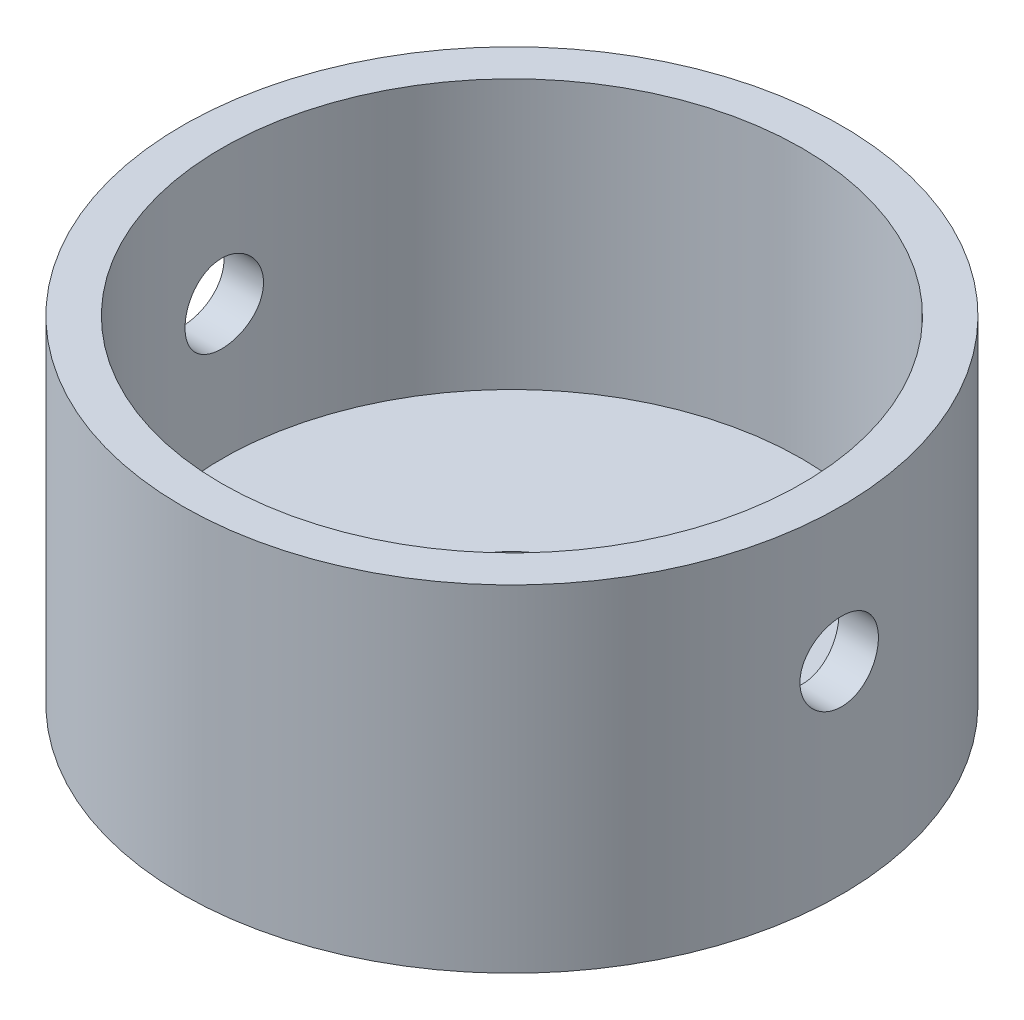
SolidWorks part; units mm, degrees
ref_plane "Front Plane" through (0, 0, 0) normal (0, 0, 1) x (1, 0, 0)
ref_plane "Top Plane" through (0, 0, 0) normal (0, 1, 0) x (1, 0, 0)
ref_plane "Right Plane" through (0, 0, 0) normal (1, 0, 0) x (0, 0, -1)
sketch "Sketch1" plane through (0, 0, 0) normal (0, 1, 0) x (1, 0, 0)
  circle A0 centre (0, 0) radius 12.7 construction
  circle A1 centre (0, 0) radius 14.7
  dimension "D1" = 25.4
  dimension "D2" = 2
extrude "Boss-Extrude1" add sketch "Sketch1" along normal blind 15
sketch "Sketch2" plane through (0, 15, 0) normal (0, 1, 0) x (1, 0, 0)
  circle A0 centre (0, 0) radius 12.95
  dimension "D1" = 25.9
extrude "Cut-Extrude1" cut sketch "Sketch2" against normal offset from surface (12 mm away) 3 up to face at (0, 0, 14.7)
sketch "Sketch3" plane through (0, 0, 0) normal (1, 0, 0) x (0, 0, -1)
  line L0 (0, 15) -> (0, 9) construction
  line L1 (12.95, 15) -> (-12.95, 15) construction
  circle A0 centre (0, 9) radius 1.75
  dimension "D2" = 3.5
  dimension "D1" = 6
extrude "Cut-Extrude2" cut sketch "Sketch3" against normal through all both and the other way through all
sketch "Sketch4" plane through (0, 0, 0) normal (0, -1, 0) x (1, 0, 0)
  circle A0 centre (0, 0) radius 4.1
  dimension "D1" = 8.2
extrude "Cut-Extrude3" cut sketch "Sketch4" against normal through all
